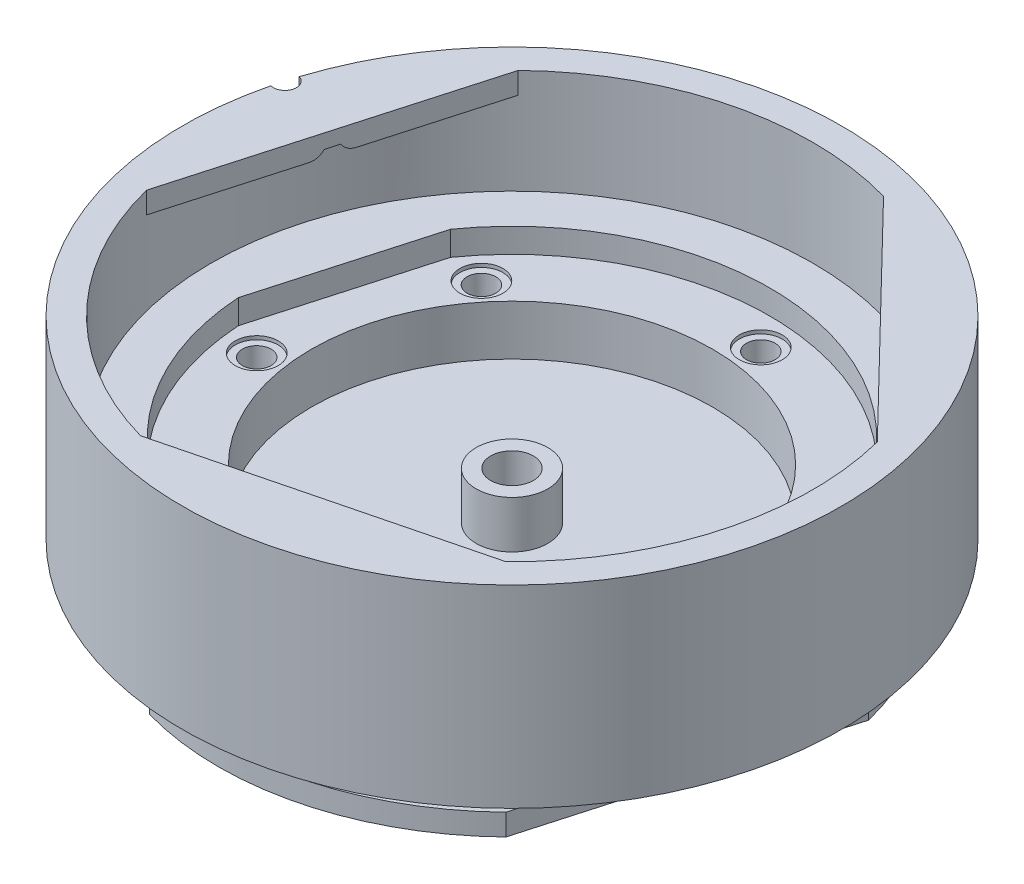
SolidWorks part; units mm, degrees
ref_plane "Front" through (0, 0, 0) normal (0, 0, 1) x (1, 0, 0)
ref_plane "Top" through (0, 0, 0) normal (0, 1, 0) x (1, 0, 0)
ref_plane "Right" through (0, 0, 0) normal (1, 0, 0) x (0, 0, -1)
sketch "Sketch1" plane through (0, 0, 0) normal (0, 1, 0) x (1, 0, 0)
  circle A0 centre (0, 0) radius 20.5
extrude "Boss-Extrude1" add sketch "Sketch1" along normal blind 1.5
sketch "Sketch2" plane through (0, 1.5, 0) normal (0, 1, 0) x (1, 0, 0)
  line L0 (-12.1923, 12.5538) -> (-12.889, 13.2712)
  line L1 (-16.9681, -4.2819) -> (-17.9377, -4.5266)
  line L2 (16.9681, 4.2819) -> (17.9377, 4.5266)
  line L3 (4.7758, 16.8357) -> (5.0487, 17.7978)
  line L4 (-4.7758, -16.8357) -> (-5.0487, -17.7978)
  line L5 (12.1923, -12.5538) -> (12.889, -13.2712)
  line L6 (-14.2824, 14.7059) -> (5.5945, 19.7219)
  line L7 (19.8769, 5.016) -> (14.2824, -14.7059)
  line L8 (-19.8769, -5.016) -> (-5.5945, -19.7219)
  line L9 (0, 0) -> (-14.2824, 14.7059) construction
  arc A0 (-19.8769, -5.016) -> (-5.5945, -19.7219) centre (0, 0) ccw
  arc A1 (-12.889, 13.2712) -> (-17.9377, -4.5266) centre (0, 0) ccw
  arc A2 (-12.1923, 12.5538) -> (-16.9681, -4.2819) centre (0, 0) ccw
  arc A3 (17.9377, 4.5266) -> (5.0487, 17.7978) centre (0, 0) ccw
  arc A4 (16.9681, 4.2819) -> (4.7758, 16.8357) centre (0, 0) ccw
  arc A5 (-5.0487, -17.7978) -> (12.889, -13.2712) centre (0, 0) ccw
  arc A6 (-4.7758, -16.8357) -> (12.1923, -12.5538) centre (0, 0) ccw
  arc A7 (14.2824, -14.7059) -> (19.8769, 5.016) centre (0, 0) ccw
  arc A8 (5.5945, 19.7219) -> (-14.2824, 14.7059) centre (0, 0) ccw
  point P13 (0, 0)
  dimension "D2" = 3
  dimension "D1" = 60
extrude "Cut-Extrude1" cut sketch "Sketch2" against normal blind 11
sketch "Sketch3" plane through (0, 1.5, 0) normal (0, 1, 0) x (1, 0, 0)
  circle A1 centre (0, 0) radius 17.5
extrude "Boss-Extrude2" add sketch "Sketch3" along normal blind 2
sketch "Sketch4" plane through (0, 3.5, 0) normal (0, 1, 0) x (1, 0, 0)
  circle A1 centre (0, 0) radius 23
extrude "Boss-Extrude3" add sketch "Sketch4" along normal blind 1
sketch "Sketch5" plane through (0, 4.5, 0) normal (0, 1, 0) x (1, 0, 0)
  circle A0 centre (0, 0) radius 23
  circle A1 centre (0, 0) radius 21
extrude "Boss-Extrude4" add sketch "Sketch5" along normal blind 11
sketch "Sketch6" plane through (0, 15.5, 0) normal (0, 1, 0) x (1, 0, 0)
  line L0 (0, 0) -> (-4.4043, 17.4529) construction
  line L2 (0, 0) -> (17.3168, -4.9122) construction
  line L5 (0, 0) -> (-12.9125, -12.5407) construction
  line L6 (14.6308, -15.0646) -> (-5.7309, -20.2029)
  line L7 (-20.3617, -5.1383) -> (-14.6308, 15.0646)
  line L8 (5.7309, 20.2029) -> (20.3617, 5.1383)
  circle A1 centre (0, 0) radius 23
  arc A4 (14.6308, -15.0646) -> (20.3617, 5.1383) centre (0, 0) ccw
  arc A5 (-20.3617, -5.1383) -> (-5.7309, -20.2029) centre (0, 0) ccw
  arc A6 (5.7309, 20.2029) -> (-14.6308, 15.0646) centre (0, 0) ccw
  point P14 (0, 0)
  point P18 (0, 0)
  point P22 (0, 0)
  dimension "D1" = 3
extrude "Boss-Extrude6" add sketch "Sketch6" along normal blind 1.5
sketch "Sketch7" plane through (0, 1.5, 0) normal (0, 1, 0) x (1, 0, 0)
  line L0 (0, 0) -> (4.2819, -16.9681) construction
  line L1 (4.0555, -18.05) -> (4.494, -20.0014)
  line L2 (4.9946, -17.813) -> (5.5346, -19.7388)
  arc A0 (-4.7758, -16.8357) -> (12.1923, -12.5538) centre (0, 0) ccw construction
  arc A1 (4.494, -20.0014) -> (5.5346, -19.7388) centre (0, 0) ccw
  arc A3 (4.0555, -18.05) -> (4.9946, -17.813) centre (0, 0) ccw
  dimension "D1" = 1.5
extrude "Boss-Extrude7" add sketch "Sketch7" along normal blind 0.8
fillet "Fillet3" radius 0.4 2 edges at (5.2646, 2.3, 18.7759) (4.2747, 2.3, 19.0257) first distance on face at (5.2646, 1.9, 18.7759) first distance on face at (4.2747, 1.9, 19.0257)
pattern_circular "CirPattern4" count 3 over 360 about axis through (0, 3.5, 0) along (0, 1, 0) of "Boss-Extrude7", "Fillet3"
ref_plane "Plane1" through (0, 15, 0) normal (0, 1, 0) x (1, 0, 0)
sketch "草图1" plane through (0, 17, 0) normal (0, 1, 0) x (1, 0, 0)
  line L0 (0, 0) -> (-12.5538, -12.1923) construction
  line L1 (0, 0) -> (-4.2819, 16.9681) construction
  line L2 (0, 0) -> (16.8357, -4.7758) construction
  circle A0 centre (0, 0) radius 18 construction
  circle A1 centre (0, 0) radius 17.5 construction
  circle A2 centre (0, 0) radius 18
  circle A3 centre (0, 0) radius 17
  point P9 (0, 0)
  dimension "D1" = 3
ref_plane "基准面1" through (0, 15, 0) normal (0, 1, 0) x (1, 0, 0)
sketch "草图9" plane through (0, 15, 0) normal (0, 1, 0) x (1, 0, 0)
  line L0 (0, 0) -> (5.016, -19.8769) construction
  line L3 (15.4424, 14.2314) -> (12.8687, 11.8595)
  line L4 (14.6764, 15.0201) -> (12.2303, 12.5167)
  arc A0 (4.494, -20.0014) -> (5.5346, -19.7388) centre (0, 0) ccw construction
  arc A5 (12.8687, 11.8595) -> (12.2303, 12.5167) centre (0, 0) ccw
  arc A6 (15.4424, 14.2314) -> (14.6764, 15.0201) centre (0, 0) ccw
  point P15 (0, 0)
extrude "切除-拉伸14" cut sketch "草图9" against normal blind 1 and the other way blind 1
fillet "圆角4" radius 1 2 edges at (14.4102, 15.5, -13.2802) (13.6954, 15.5, -14.0162)
pattern_circular "阵列(圆周)2" count 3 over 360 about axis through (0, 17, 0) along (0, 1, 0) of "切除-拉伸14", "圆角4"
sketch "草图15" plane through (0, 4.5, 0) normal (0, 1, 0) x (1, 0, 0)
  line L0 (0, 0) -> (-4.2819, 16.9681) construction
  circle A0 centre (0, 0) radius 21
  circle A5 centre (0, 0) radius 14
extrude "凸台-拉伸6" add sketch "草图15" along normal blind 3.5
sketch "草图16" plane through (0, 4.5, 0) normal (0, 1, 0) x (1, 0, 0)
  circle A0 centre (0, 0) radius 2.5
extrude "凸台-拉伸7" add sketch "草图16" along normal blind 3.3
sketch "草图17" plane through (0, 7.8, 0) normal (0, 1, 0) x (1, 0, 0)
  circle A0 centre (0, 0) radius 1.49
extrude "切除-拉伸17" cut sketch "草图17" against normal blind 32
sketch "草图20" plane through (0, 8, 0) normal (0, 1, 0) x (1, 0, 0)
  circle A0 centre (0, 0) radius 21
  circle A1 centre (0, 0) radius 18
extrude "凸台-拉伸8" add sketch "草图20" along normal blind 1.7
sketch "草图21" plane through (0, 8, 0) normal (0, 1, 0) x (1, 0, 0)
  line L0 (0, 0) -> (16.6631, -4.7268) construction
  line L2 (0, 0) -> (-7.1059, -25.0502) construction
  circle A0 centre (-15.6614, -2.1579) radius 1.5
  circle A1 centre (-6.9509, -14.2656) radius 1.5
  circle A2 centre (12.1955, -10.06) radius 1.5
  circle A3 centre (15.6614, 2.1579) radius 1.5
  circle A4 centre (1.575, 15.7905) radius 1.5
  circle A5 centre (-12.1955, 10.06) radius 1.5
  circle A6 centre (0, 0) radius 1.49 construction
  circle A7 centre (1.4334, -0.4066) radius 0.5 construction
  dimension "D1" = 14.478
  dimension "D3" = 2.794
  dimension "D5" = 14.478
  dimension "D2" = 6.35
  dimension "D4" = 15.621
  dimension "D6" = 6.35
extrude "切除-拉伸18" cut sketch "草图21" against normal blind 0.25
sketch "草图22" plane through (0, 7.75, 0) normal (0, 1, 0) x (1, 0, 0)
  line L0 (0, 0) -> (16.9497, -4.8081) construction
  circle A1 centre (-15.6614, -2.1579) radius 1
  circle A2 centre (-6.9509, -14.2656) radius 1
  circle A3 centre (12.1955, -10.06) radius 1
  circle A4 centre (15.6614, 2.1579) radius 1
  circle A5 centre (1.575, 15.7905) radius 1
  circle A6 centre (-12.1955, 10.06) radius 1
extrude "切除-拉伸19" cut sketch "草图22" against normal blind 10
sketch "草图24" plane through (0, 17, 0) normal (0, 1, 0) x (1, 0, 0)
  line L0 (0, 0) -> (-17.4962, 4.9631) construction
  circle A0 centre (-22.127, 6.2767) radius 0.8
  circle A1 centre (0, 0) radius 23 construction
extrude "切除-拉伸20" cut sketch "草图24" against normal blind 18
sketch "草图25" plane through (0, 8, 0) normal (0, 1, 0) x (1, 0, 0)
  line L0 (0, 0) -> (-25.0797, 7.1143) construction
  line L1 (-14.689, 10.4035) -> (-17.9638, -1.141)
  arc A0 (-14.689, 10.4035) -> (-17.9638, -1.141) centre (0, 0) ccw
extrude "凸台-拉伸9" add sketch "草图25" along normal blind 1.7
